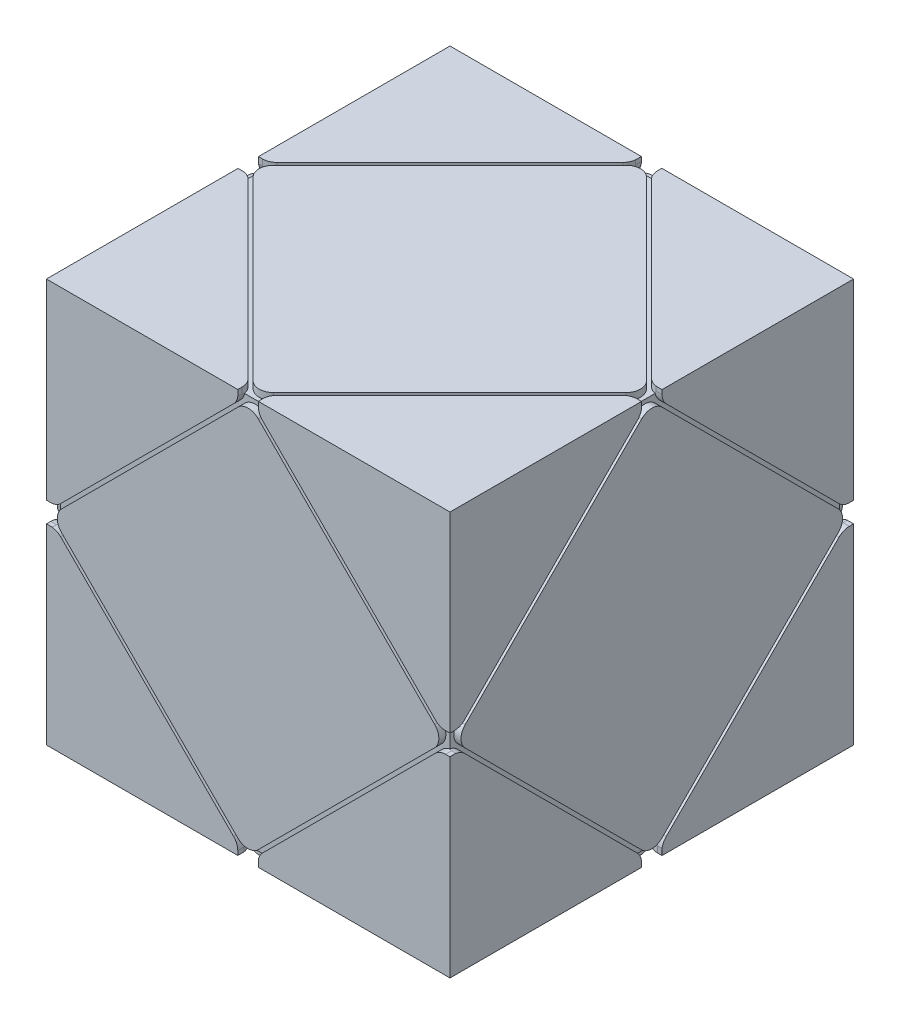
SolidWorks part; units mm, degrees
note: '?' marks a value the reader was unsure of.
ref_plane "Front Plane" through (0, 0, 0) normal (0, 0, 1) x (1, 0, 0)
ref_plane "Top Plane" through (0, 0, 0) normal (0, 1, 0) x (1, 0, 0)
ref_plane "Right Plane" through (0, 0, 0) normal (1, 0, 0) x (0, 0, -1)
sketch "Sketch1" plane through (0, 0, 0) normal (0, 0, 1) x (1, 0, 0)
  line L1 (0, 0) -> (56, 0)
  line L2 (0, 0) -> (0, 56)
  line L3 (0, 56) -> (56, 56)
  line L4 (56, 0) -> (56, 56)
  dimension "D1" = 56
extrude "Boss-Extrude1" add sketch "Sketch1" along normal blind 56 contours L3 L4 L1 L2
sketch "Sketch3" plane through (56, 0, 0) normal (1, 0, 0) x (0, 0, -1)
  line L1 (-14, 42) -> (-14.3536, 41.6464) construction
  line L2 (-14, 14) -> (-14.3536, 14.3536) construction
  line L4 (-42, 14) -> (-41.6464, 14.3536) construction
  line L6 (-41.6464, 41.6464) -> (-68.6451, 14.6478) construction
  line L8 (-29.991, 54.009) -> (-53.991, 30.009)
  line L9 (-56, 0) -> (-56, 56) construction
  line L11 (-56, 0) -> (0, 0) construction
  line L12 (-26.009, 1.991) -> (-2.009, 25.991)
  line L13 (0, 0) -> (0, 56) construction
  line L14 (-1.991, 29.991) -> (-25.991, 53.991)
  line L15 (-56, 28) -> (0, 28) construction
  line L16 (-28, 56) -> (-28, 0) construction
  line L17 (-42, 42) -> (-41.6464, 41.6464) construction
  line L18 (-41.6464, 14.3536) -> (-72.043, 44.7501) construction
  line L19 (-2.1123, 29.4232) -> (-26.5768, 53.8877)
  line L20 (-2.1123, 26.5948) -> (-26.5948, 2.1123)
  line L21 (-29.4052, 53.8877) -> (-53.8877, 29.4052)
  line L22 (-29.4232, 2.1123) -> (-53.8877, 26.5768)
  line L23 (-0.6981, 28.009) -> (-55.3019, 27.991) construction
  line L24 (-27.991, 55.3019) -> (-28.009, 0.6981) construction
  line L25 (-29.4052, 55.4232) -> (-29.4052, 56)
  line L26 (-56, 56) -> (0, 56) construction
  line L27 (-29.4052, 56) -> (-26.5768, 56)
  line L28 (-26.5768, 56) -> (-26.5768, 55.4052)
  line L29 (-0.5768, 29.4052) -> (0, 29.4052)
  line L30 (0, 26.5768) -> (-0.5948, 26.5768)
  line L31 (-26.5948, 0.5768) -> (-26.5948, 0)
  line L32 (-29.4232, 0) -> (-29.4232, 0.5948)
  line L33 (-55.4232, 26.5948) -> (-56, 26.5948)
  line L34 (-56, 29.4232) -> (-55.4052, 29.4232)
  line L35 (0, 29.4052) -> (0, 26.5768)
  line L36 (-54.009, 26.009) -> (-30.009, 2.009)
  line L37 (-26.5948, 0) -> (-29.4232, 0)
  line L38 (-56, 26.5948) -> (-56, 29.4232)
  line L39 (-29.4052, 56) -> (-26.5768, 56)
  arc A0 (-26.5948, 2.1123) -> (-29.4232, 2.1123) centre (-28.009, 3.5265) cw
  arc A1 (-2.1123, 26.5948) -> (-2.1123, 29.4232) centre (-3.5265, 28.009) ccw
  arc A2 (-26.5768, 53.8877) -> (-29.4052, 53.8877) centre (-27.991, 52.4735) ccw
  arc A3 (-53.8877, 29.4052) -> (-53.8877, 26.5768) centre (-52.4735, 27.991) ccw
  arc A4 (-25.991, 53.991) -> (-26.5768, 55.4052) centre (-24.5768, 55.4052) cw
  arc A5 (-29.991, 54.009) -> (-29.4052, 55.4232) centre (-31.4052, 55.4232) ccw
  arc A6 (-1.991, 29.991) -> (-0.5768, 29.4052) centre (-0.5768, 31.4052) ccw
  arc A7 (-2.009, 25.991) -> (-0.5948, 26.5768) centre (-0.5948, 24.5768) cw
  arc A8 (-26.009, 1.991) -> (-26.5948, 0.5768) centre (-24.5948, 0.5768) ccw
  arc A9 (-30.009, 2.009) -> (-29.4232, 0.5948) centre (-31.4232, 0.5948) cw
  arc A10 (-54.009, 26.009) -> (-55.4232, 26.5948) centre (-55.4232, 24.5948) ccw
  arc A11 (-53.991, 30.009) -> (-55.4052, 29.4232) centre (-55.4052, 31.4232) cw
  point P14 (0, 28)
  point P17 (-28, 0)
  point P20 (-56, 28)
  point P23 (-28, 56)
  point P25 (-28, 28)
  line M9 (0, 0) -> (0, 56)
  line M10 (0, 56) -> (-56, 56)
  line M11 (-56, 56) -> (-56, 0)
  line M12 (-56, 0) -> (0, 0)
  dimension "D1" = 0.5
  dimension "D3" = 2
  dimension "D4" = 2
  dimension "D2" = 0.5
  dimension "D5" = 4
  dimension "D6" = 4
extrude "Cut-Extrude4" cut sketch "Sketch3" against normal blind 1 contours L8 A11 L34 L33 A10 L36 A9 L32 L31 A8 L12 A7 L30 L29 A6 L14 A4 L28 L25 A5 A3 L21 A2 L19 A1 L20 A0 L22 M11 M12 M9 M10
pattern_circular "CirPattern1" count 4 over 360 about axis through (27.9752, 28, 0) along (0, 0, 1) of "Cut-Extrude4"
pattern_circular "CirPattern2" count 4 over 360 about axis through (27.9752, 0, 28) along (0, 1, 0) of "Cut-Extrude4"
ref_axis "Mid Axis" through (56, 56, 0) along (-0.5774, -0.5774, 0.5774)?
ref_plane "Cube Vert Midplane" through (0, 0, 0) normal (-0.7071, 0.7071, 0) x (0.7071, 0.7071, 0)
ref_plane "Cube Z Midplane" through (0, 0, 28) normal (0, 0, -1) x (-1, 0, 0)
ref_axis "Corner 1 Centerline" through (56, 0, 0) along (-0.5774, 0.5774, 0.5774)?
ref_axis "Corner 2 Centerline" through (0, 0, 56) along (0.5774, 0.5774, -0.5774)?
ref_axis "Corner 3 Centerline" through (0, 56, 0) along (0.5774, -0.5774, 0.5774)?
ref_axis "Corner 4 Centerline" through (56, 56, 56) along (-0.5774, -0.5774, -0.5774)?
